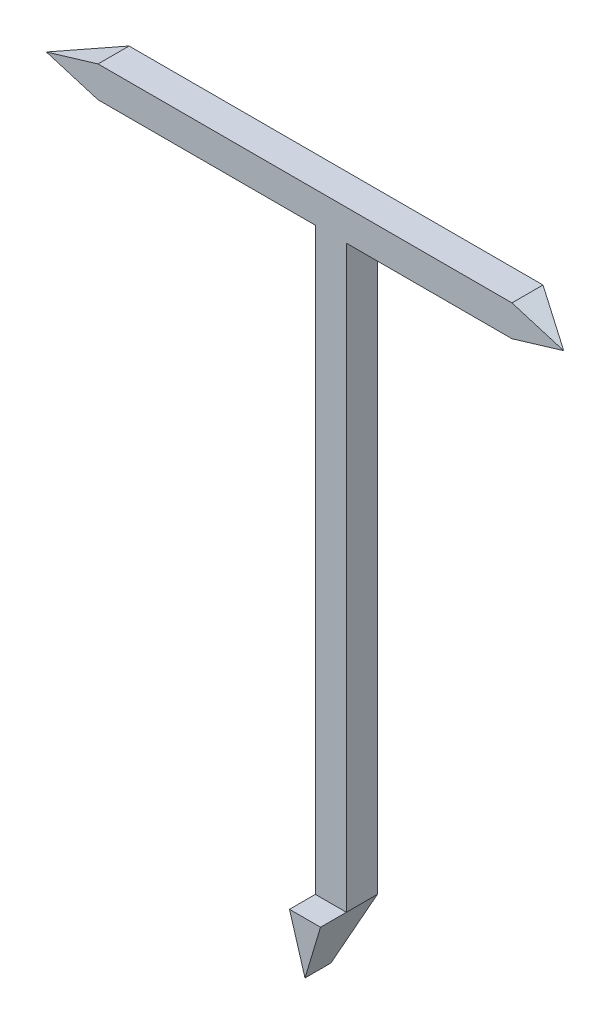
SolidWorks part; units mm, degrees
ref_plane "Front Plane" through (0, 0, 0) normal (0, 0, 1) x (1, 0, 0)
ref_plane "Top Plane" through (0, 0, 0) normal (0, 1, 0) x (1, 0, 0)
ref_plane "Right Plane" through (0, 0, 0) normal (1, 0, 0) x (0, 0, -1)
sketch "Sketch1" plane through (0, 0, 0) normal (0, 0, 1) x (1, 0, 0)
  line L0 (-63.5, 0) -> (63.5, 0) construction
  line L1 (6.35, 0) -> (6.35, -158.75) construction
  line L2 (-63.5, 0) -> (-50.8, 3.81)
  line L3 (-50.8, 3.81) -> (50.8, 3.81)
  line L4 (50.8, 3.81) -> (63.5, 0)
  line L5 (63.5, 0) -> (50.8, -3.81)
  line L6 (50.8, -3.81) -> (10.16, -3.81)
  line L7 (-50.8, -3.81) -> (-63.5, 0)
  line L8 (6.35, -158.75) -> (2.54, -146.05)
  line L9 (6.35, -158.75) -> (10.16, -146.05)
  line L10 (2.54, -146.05) -> (2.54, -3.81)
  line L11 (10.16, -146.05) -> (10.16, -3.81)
  line L12 (2.54, -3.81) -> (-50.8, -3.81)
  point P2 (0, 0)
  dimension "D1" = 127
  dimension "D2" = 69.85
  dimension "D3" = 158.75
  dimension "D4" = 12.7
  dimension "D5" = 12.7
  dimension "D6" = 7.62
  dimension "D7" = 3.81
  dimension "D8" = 12.7
  dimension "D9" = 7.62
  dimension "D10" = 3.81
ref_plane "Plane1" through (6.35, 0, 0) normal (1, 0, 0) x (0, 0, -1)
sketch "Sketch2" plane through (6.35, 0, 0) normal (1, 0, 0) x (0, 0, -1)
  line L0 (0, -158.75) -> (-6.35, -158.75)
  dimension "D1" = 6.35
extrude "Boss-Extrude1" add sketch "Sketch1" against normal blind 7.62
sketch "Sketch3" plane through (0, 3.81, 0) normal (0, 1, 0) x (1, 0, 0)
  line L0 (-63.5, 0) -> (-50.8, 7.62)
  line L1 (-50.8, 7.62) -> (-63.5, 7.62)
  line L2 (-63.5, 7.62) -> (-63.5, 0)
  line L3 (63.5, 7.62) -> (63.5, 0)
  line L4 (63.5, 0) -> (50.8, 7.62)
  line L5 (50.8, 7.62) -> (63.5, 7.62)
extrude "Cut-Extrude1" cut sketch "Sketch3" against normal through all
sketch "Sketch4" plane through (10.16, 0, 0) normal (1, 0, 0) x (0, 0, -1)
  line L0 (0, -158.75) -> (7.62, -146.05)
  line L1 (7.62, -146.05) -> (7.62, -158.75)
  line L2 (7.62, -158.75) -> (0, -158.75)
extrude "Cut-Extrude2" cut sketch "Sketch4" against normal through all
sketch "Sketch6" plane through (0, 0, 0) normal (0, 0, 1) x (1, 0, 0)
  line L0 (2.54, -146.05) -> (10.16, -146.05)
  line L1 (10.16, -146.05) -> (6.35, -158.75)
  line L2 (6.35, -158.75) -> (2.54, -146.05)
  point P4 (38.4979, -146.05)
extrude "Boss-Extrude3" add sketch "Sketch6" along normal up to vertex (6.35 mm away) up to point (6.35, -158.75, 6.35)
